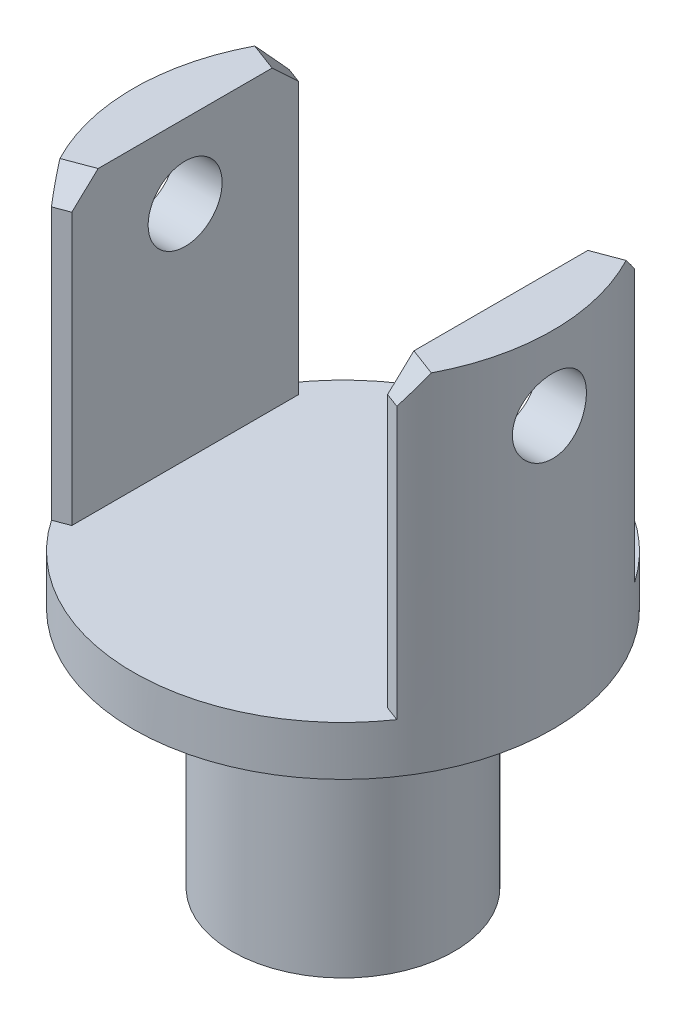
SolidWorks part; units mm, degrees
ref_plane "Front Plane" through (0, 0, 0) normal (0, 0, 1) x (1, 0, 0)
ref_plane "Top Plane" through (0, 0, 0) normal (0, 1, 0) x (1, 0, 0)
ref_plane "Right Plane" through (0, 0, 0) normal (1, 0, 0) x (0, 0, -1)
sketch "Sketch1" plane through (0, 0, 0) normal (0, 1, 0) x (1, 0, 0)
  circle A0 centre (0, 0) radius 42.5
  dimension "D1" = 85
extrude "Boss-Extrude1" add sketch "Sketch1" along normal blind 10
sketch "Sketch2" plane through (0, 10, 0) normal (0, 1, 0) x (1, 0, 0)
  line L0 (32, 27.9687) -> (32, -27.9687)
  circle A1 centre (0, 0) radius 42.5
  arc A2 (32, -27.9687) -> (32, 27.9687) centre (0, 0) ccw
  dimension "D2" = 32
  dimension "D1" = 0
extrude "Boss-Extrude2" add sketch "Sketch2" along normal blind 60
sketch "Sketch3" plane through (32, 0, 0) normal (-1, 0, 0) x (0, 0, 1)
  line L0 (0, -50) -> (0, 50) construction
  line L1 (-27.9687, 70) -> (27.9687, 70) construction
  circle A0 centre (0, 55) radius 7.5
  dimension "D1" = 15
  dimension "D2" = 15
extrude "Cut-Extrude1" cut sketch "Sketch3" against normal through all
mirror "Mirror1" about plane through (0, 0, 0) normal (1, 0, 0) of "Boss-Extrude2", "Cut-Extrude1"
sketch "Sketch4" plane through (0, 0, 0) normal (0, -1, 0) x (1, 0, 0)
  circle A0 centre (0, 0) radius 22.5
  dimension "D1" = 45
extrude "Boss-Extrude3" add sketch "Sketch4" along normal blind 49
chamfer "Chamfer1" distance 5 4 edges at (-32, 40, -27.9687) (-32, 40, 27.9687)
chamfer "Chamfer2" distance 5 angle 45 4 edges at (33.5039, 70, -23.5333) (33.5039, 70, 23.5333) (-33.5039, 70, -23.5333) (-33.5039, 70, 23.5333)
